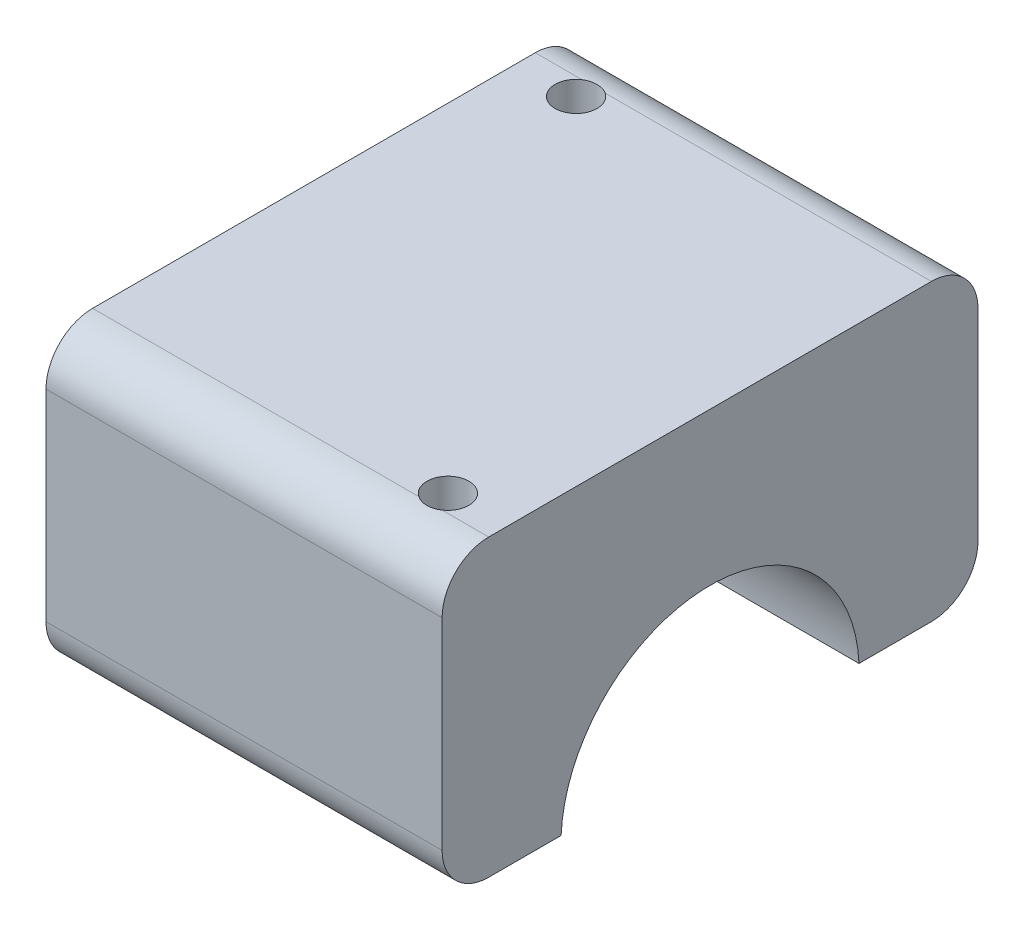
SolidWorks part; units mm, degrees
ref_plane "Front Plane" through (0, 0, 0) normal (0, 0, 1) x (1, 0, 0)
ref_plane "Top Plane" through (0, 0, 0) normal (0, 1, 0) x (1, 0, 0)
ref_plane "Right Plane" through (0, 0, 0) normal (1, 0, 0) x (0, 0, -1)
sketch "Sketch1" plane through (0, 0, 0) normal (1, 0, 0) x (0, 0, -1)
  line L0 (-19, 0.6) -> (19, 0.6)
  line L1 (23, 4.6) -> (23, 21.896)
  line L2 (19, 25.896) -> (-19, 25.896)
  line L3 (-23, 21.896) -> (-23, 4.6)
  arc A0 (19, 0.6) -> (23, 4.6) centre (19, 4.6) ccw
  arc A1 (23, 21.896) -> (19, 25.896) centre (19, 21.896) ccw
  arc A2 (-19, 25.896) -> (-23, 21.896) centre (-19, 21.896) ccw
  arc A3 (-23, 4.6) -> (-19, 0.6) centre (-19, 4.6) ccw
extrude "Boss-Extrude1" add sketch "Sketch1" along normal mid plane 34
sketch "Sketch2" plane through (0, 0, 0) normal (1, 0, 0) x (0, 0, -1)
  circle A0 centre (0, 0) radius 12.8
extrude "Cut-Extrude1" cut sketch "Sketch2" against normal through all and the other way through all
ref_plane "Plane1" through (0, 0.6, 0) normal (0, 1, 0) x (1, 0, 0)
sketch "Sketch3" plane through (0, 0.6, 0) normal (0, 1, 0) x (1, 0, 0)
  circle A0 centre (12, -17.5) radius 1.8
  circle A1 centre (-12, 17.5) radius 1.8
extrude "Cut-Extrude2" cut sketch "Sketch3" along normal blind 25.896
